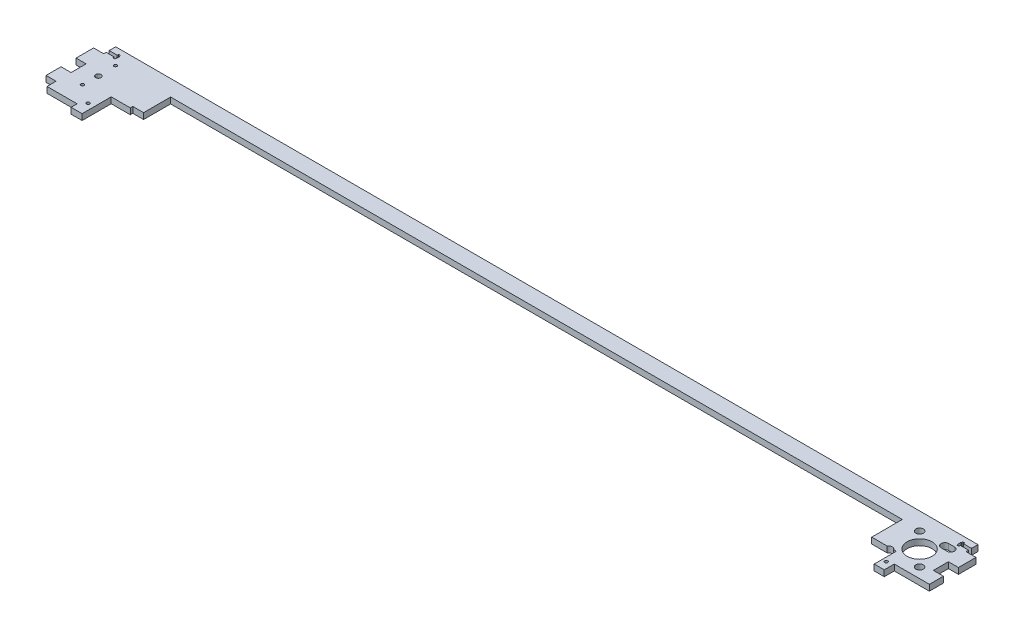
SolidWorks part; units mm, degrees
ref_plane "Płaszczyzna przednia" through (0, 0, 0) normal (0, 0, 1) x (1, 0, 0)
ref_plane "Płaszczyzna górna" through (0, 0, 0) normal (0, 1, 0) x (1, 0, 0)
ref_plane "Płaszczyzna prawa" through (0, 0, 0) normal (1, 0, 0) x (0, 0, -1)
sketch "Szkic1" plane through (0, -418.8763, -418.8763) normal (0, 1, 0) x (1, 0, 0)
  line L1 (-1145.3685, -408.8763) -> (-265.3685, -408.8763)
  line L2 (-1145.3685, -483.3763) -> (-1145.3685, -408.8763)
  line L3 (-265.3685, -408.8763) -> (-265.3685, -483.3763)
  line L4 (-1145.3685, -483.3763) -> (-265.3685, -483.3763)
  line L5 (-334.8685, -424.8763) -> (-1070.8685, -424.8763)
  line L6 (-334.8685, -424.8763) -> (-334.8685, -452.8763)
  line L7 (-334.8685, -452.8763) -> (-1070.8685, -452.8763)
  line L8 (-1070.8685, -424.8763) -> (-1070.8685, -452.8763)
  line L10 (-482.1641, -408.8763) -> (-356.3685, -408.8763) construction
  line L11 (-265.3685, -1108.8763) -> (-265.3685, -528.8763) construction
  dimension "D1" = 0
  dimension "D2" = 0
  dimension "D3" = 74.5
  dimension "D4" = 880
  dimension "D5" = 30.5
  dimension "D6" = 28
  dimension "D7" = 69.5
  dimension "D8" = 74.5
extrude "Dodanie-wyciągnięcie2" add sketch "Szkic1" along normal blind 3 and the other way blind 3
sketch "Szkic2" plane through (0, 0, 64.5) normal (0, 0, 1) x (1, 0, 0)
  line L0 (-1145.3685, -415.8763) -> (-265.3685, -415.8763) construction
  line L1 (-1145.3685, -421.8763) -> (-1105.3685, -421.8763)
  line L2 (-1145.3685, -421.8763) -> (-1145.3685, -415.8763)
  line L3 (-1145.3685, -415.8763) -> (-1105.3685, -415.8763)
  line L4 (-1105.3685, -421.8763) -> (-1105.3685, -415.8763)
  dimension "D1" = 40
extrude "Wytnij-wyciągnięcie1" cut sketch "Szkic2" against normal blind 6
pattern_linear "Szyk liniowy1" count 13 spacing 91 along (1, 0, 0) of "Wytnij-wyciągnięcie1"
sketch "Szkic3" plane through (0, -415.8763, 0) normal (0, 1, 0) x (1, 0, 0)
  line L0 (-1105.3685, -58.5) -> (-1145.3685, -58.5) construction
  line L1 (-1032.8185, -58.5) -> (-1035.9185, -58.5)
  line L2 (-1032.8185, -58.5) -> (-1032.8185, -54.5)
  line L3 (-1032.8185, -52) -> (-1035.9185, -52)
  line L4 (-1035.9185, -58.5) -> (-1035.9185, -54.5)
  line L5 (-1032.8185, -52.5) -> (-1032.8185, -52)
  line L6 (-1031.4435, -52.5) -> (-1032.8185, -52.5)
  line L7 (-1031.4435, -52.5) -> (-1031.4435, -54.5)
  line L8 (-1031.4435, -54.5) -> (-1032.8185, -54.5)
  line L9 (-1037.2935, -52.5) -> (-1037.2935, -54.5)
  line L10 (-1035.9185, -52.5) -> (-1037.2935, -52.5)
  line L11 (-1035.9185, -52.5) -> (-1035.9185, -52)
  line L12 (-1035.9185, -54.5) -> (-1037.2935, -54.5)
  line L14 (-1054.3685, -58.5) -> (-1054.3685, -64.5) construction
  point P14 (-1034.3685, -58.5)
  dimension "D1" = 6.5
  dimension "D2" = 3.1
  dimension "D3" = 5.85
  dimension "D4" = 1.375
  dimension "D5" = 0.5
  dimension "D6" = 2
  dimension "D7" = 20
extrude "Wytnij-wyciągnięcie2" cut sketch "Szkic3" against normal blind 6
sketch "Szkic4" plane through (0, -415.8763, 0) normal (0, 1, 0) x (1, 0, 0)
  line L0 (-1145.3685, 10) -> (-1145.3685, -58.5) construction
  line L1 (-1145.3685, -19.5) -> (-1135.3685, -19.5)
  line L2 (-1145.3685, -19.5) -> (-1145.3685, -34.5)
  line L3 (-1145.3685, -34.5) -> (-1135.3685, -34.5)
  line L4 (-1135.3685, -19.5) -> (-1135.3685, -34.5)
  line L6 (-1105.3685, -58.5) -> (-1145.3685, -58.5) construction
  line L8 (-1145.3685, -58.5) -> (-1135.3685, -58.5)
  line L9 (-1145.3685, -58.5) -> (-1145.3685, -49.5)
  line L10 (-1145.3685, -49.5) -> (-1135.3685, -49.5)
  line L11 (-1135.3685, -58.5) -> (-1135.3685, -49.5)
  line L12 (-1145.3685, 10) -> (-1135.3685, 10)
  line L13 (-1145.3685, 10) -> (-1145.3685, -2)
  line L14 (-1145.3685, -2) -> (-1135.3685, -2)
  line L15 (-1135.3685, 10) -> (-1135.3685, -2)
  dimension "D1" = 15
  dimension "D2" = 24
  dimension "D3" = 10
  dimension "D4" = 10
  dimension "D5" = 9
  dimension "D6" = 10
  dimension "D7" = 12
extrude "Wytnij-wyciągnięcie3" cut sketch "Szkic4" against normal blind 6
sketch "Szkic5" plane through (0, -415.8763, 0) normal (0, 1, 0) x (1, 0, 0)
  line L0 (-1135.3685, -34.5) -> (-1135.3685, -19.5) construction
  line L1 (-1135.3685, 3.55) -> (-1127.3685, 3.55)
  line L2 (-1135.3685, 3.55) -> (-1135.3685, 0.45)
  line L3 (-1135.3685, 0.45) -> (-1127.3685, 0.45)
  line L4 (-1124.8685, 3.55) -> (-1124.8685, 0.45)
  line L5 (-1125.3685, 3.55) -> (-1125.3685, 4.925)
  line L6 (-1125.3685, -0.925) -> (-1127.3685, -0.925)
  line L7 (-1125.3685, -0.925) -> (-1125.3685, 0.45)
  line L8 (-1125.3685, 4.925) -> (-1127.3685, 4.925)
  line L9 (-1127.3685, -0.925) -> (-1127.3685, 0.45)
  line L10 (-1125.3685, 0.45) -> (-1124.8685, 0.45)
  line L11 (-1127.3685, 3.55) -> (-1127.3685, 4.925)
  line L12 (-1125.3685, 3.55) -> (-1124.8685, 3.55)
  line L13 (-265.3685, 10) -> (-1135.3685, 10) construction
  point P14 (-1135.3685, 2)
  dimension "D1" = 3.1
  dimension "D2" = 0.5
  dimension "D3" = 5.85
  dimension "D4" = 1.375
  dimension "D5" = 2
  dimension "D6" = 10.5
  dimension "D7" = 8
extrude "Wytnij-wyciągnięcie4" cut sketch "Szkic5" against normal blind 6
ref_plane "Płaszczyzna1" through (-705.3685, 0, 0) normal (-1, 0, 0) x (0, 0, 1)
mirror "Lustro1" about plane through (-705.3685, 0, 0) normal (-1, 0, 0) of "Wytnij-wyciągnięcie4", "Wytnij-wyciągnięcie3"
sketch "Szkic6" plane through (0, -421.8763, 0) normal (0, -1, 0) x (1, 0, 0)
  circle A0 centre (-1118.7056, 24) radius 2.5 construction
  circle A8 centre (-1119.2648, 6.2898) radius 1.55 construction
  circle A9 centre (-1118.7056, 24) radius 8
  circle A10 centre (-1118.7056, 24) radius 2.7
  circle A11 centre (-1119.2648, 39.2898) radius 1.55 construction
  circle A12 centre (-1119.2648, 6.2898) radius 1.55
  circle A13 centre (-1119.2648, 39.2898) radius 1.55
  dimension "D1" = 0
sketch "Szkic8" plane through (0, -421.8763, 0) normal (0, -1, 0) x (1, 0, 0)
  circle A0 centre (-1119.2648, 39.2898) radius 1.55 construction
  circle A1 centre (-1119.2648, 39.2898) radius 1.55
  circle A4 centre (-1119.2648, 6.2898) radius 1.55 construction
  circle A7 centre (-1119.2648, 6.2898) radius 1.55
  circle A8 centre (-1118.7056, 24) radius 2.7 construction
  circle A10 centre (-1118.7056, 24) radius 2.7
extrude "Wytnij-wyciągnięcie5" cut sketch "Szkic8" against normal blind 6
sketch "Szkic9" plane through (0, -415.8763, 0) normal (0, 1, 0) x (1, 0, 0)
  circle A0 centre (-300.7063, -22.93) radius 2.5 construction
  circle A2 centre (-300.7063, -22.93) radius 12.5
  dimension "D1" = 25
  dimension "D2" = 0
extrude "Wytnij-wyciągnięcie6" cut sketch "Szkic9" against normal blind 6
sketch "Szkic10" plane through (0, -421.8763, 0) normal (0, -1, 0) x (1, 0, 0)
  circle A0 centre (-285.2063, 38.43) radius 1.55 construction
  circle A1 centre (-285.2063, 7.43) radius 1.55 construction
  circle A2 centre (-316.2063, 38.43) radius 1.55 construction
  circle A3 centre (-316.2063, 7.43) radius 1.55 construction
  circle A4 centre (-285.2063, 38.43) radius 1.55
  circle A5 centre (-285.2063, 7.43) radius 1.55
  circle A6 centre (-316.2063, 38.43) radius 1.55
  circle A7 centre (-316.2063, 7.43) radius 1.55
  circle A8 centre (-285.2063, 38.43) radius 3.75
  circle A9 centre (-285.2063, 7.43) radius 3.75
  circle A10 centre (-316.2063, 38.43) radius 3.75
  circle A11 centre (-316.2063, 7.43) radius 3.75
  dimension "D1" = 7.5
  dimension "D2" = 7.5
  dimension "D3" = 7.5
  dimension "D4" = 7.5
sketch "Szkic13" plane through (0, -415.8763, 0) normal (0, 1, 0) x (1, 0, 0)
  line L0 (-265.3685, -48.5) -> (-265.3685, -64.5)
  line L1 (-265.3685, -48.5) -> (-295.3685, -48.5)
  line L2 (-265.3685, -64.5) -> (-295.3685, -64.5)
  line L3 (-295.3685, -48.5) -> (-295.3685, -64.5)
  line L4 (-286.3685, -58.5) -> (-326.3685, -58.5) construction
  line L5 (-265.3685, -49.5) -> (-265.3685, -34.5) construction
  line L6 (-286.3685, -64.5) -> (-265.3685, -64.5) construction
  dimension "D1" = 0
  dimension "D2" = 30
  dimension "D3" = 0
  dimension "D4" = 10
extrude "Wytnij-wyciągnięcie8" cut sketch "Szkic13" against normal blind 6
pattern_linear "Szyk liniowy3" count 2 spacing 91 along (1, 0, 0) count 3 spacing 273 along (1, 0, 0) of "Wytnij-wyciągnięcie2"
sketch "Szkic14" plane through (0, -415.8763, 0) normal (0, 1, 0) x (1, 0, 0)
  line L111 (-319.9563, -36.5) -> (-1105.3685, -36.5)
  line L112 (-1105.3685, -36.5) -> (-1105.3685, -64.5)
  line L113 (-1105.3685, -64.5) -> (-1054.3685, -64.5)
  line L114 (-1054.3685, -64.5) -> (-1054.3685, -58.5)
  line L115 (-1054.3685, -58.5) -> (-1035.9185, -58.5)
  line L116 (-1035.9185, -58.5) -> (-1035.9185, -54.5)
  line L117 (-1035.9185, -54.5) -> (-1037.2935, -54.5)
  line L118 (-1037.2935, -54.5) -> (-1037.2935, -52.5)
  line L119 (-1037.2935, -52.5) -> (-1035.9185, -52.5)
  line L120 (-1035.9185, -52.5) -> (-1035.9185, -52)
  line L121 (-1035.9185, -52) -> (-1032.8185, -52)
  line L122 (-1032.8185, -52) -> (-1032.8185, -52.5)
  line L123 (-1032.8185, -52.5) -> (-1031.4435, -52.5)
  line L124 (-1031.4435, -52.5) -> (-1031.4435, -54.5)
  line L125 (-1031.4435, -54.5) -> (-1032.8185, -54.5)
  line L126 (-1032.8185, -54.5) -> (-1032.8185, -58.5)
  line L127 (-1032.8185, -58.5) -> (-1014.3685, -58.5)
  line L128 (-1014.3685, -58.5) -> (-1014.3685, -64.5)
  line L129 (-1014.3685, -64.5) -> (-963.3685, -64.5)
  line L130 (-963.3685, -64.5) -> (-963.3685, -58.5)
  line L131 (-963.3685, -58.5) -> (-944.9185, -58.5)
  line L132 (-319.9563, -36.5) -> (-1105.3685, -36.5)
  line L133 (-944.9185, -58.5) -> (-944.9185, -54.5)
  line L134 (-944.9185, -58.5) -> (-944.9185, -54.5)
  line L135 (-944.9185, -54.5) -> (-946.2935, -54.5)
  line L136 (-944.9185, -54.5) -> (-946.2935, -54.5)
  line L137 (-946.2935, -54.5) -> (-946.2935, -52.5)
  line L138 (-946.2935, -54.5) -> (-946.2935, -52.5)
  line L139 (-946.2935, -52.5) -> (-944.9185, -52.5)
  line L140 (-946.2935, -52.5) -> (-944.9185, -52.5)
  line L141 (-944.9185, -52.5) -> (-944.9185, -52)
  line L142 (-944.9185, -52.5) -> (-944.9185, -52)
  line L144 (-923.3685, -58.5) -> (-923.3685, -64.5)
  line L145 (-923.3685, -64.5) -> (-872.3685, -64.5)
  line L146 (-872.3685, -64.5) -> (-872.3685, -58.5)
  line L147 (-872.3685, -58.5) -> (-832.3685, -58.5)
  line L148 (-832.3685, -58.5) -> (-832.3685, -64.5)
  line L149 (-832.3685, -64.5) -> (-781.3685, -64.5)
  line L150 (-781.3685, -64.5) -> (-781.3685, -58.5)
  line L151 (-781.3685, -58.5) -> (-762.9185, -58.5)
  line L164 (-741.3685, -58.5) -> (-741.3685, -64.5)
  line L165 (-741.3685, -64.5) -> (-690.3685, -64.5)
  line L166 (-690.3685, -64.5) -> (-690.3685, -58.5)
  line L167 (-690.3685, -58.5) -> (-671.9185, -58.5)
  line L180 (-650.3685, -58.5) -> (-650.3685, -64.5)
  line L181 (-650.3685, -64.5) -> (-599.3685, -64.5)
  line L182 (-599.3685, -64.5) -> (-599.3685, -58.5)
  line L183 (-599.3685, -58.5) -> (-559.3685, -58.5)
  line L184 (-559.3685, -58.5) -> (-559.3685, -64.5)
  line L185 (-559.3685, -64.5) -> (-508.3685, -64.5)
  line L186 (-508.3685, -64.5) -> (-508.3685, -58.5)
  line L187 (-508.3685, -58.5) -> (-489.9185, -58.5)
  line L200 (-468.3685, -58.5) -> (-468.3685, -64.5)
  line L201 (-468.3685, -64.5) -> (-417.3685, -64.5)
  line L202 (-417.3685, -64.5) -> (-417.3685, -58.5)
  line L203 (-417.3685, -58.5) -> (-398.9185, -58.5)
  line L216 (-377.3685, -58.5) -> (-377.3685, -64.5)
  line L217 (-377.3685, -64.5) -> (-326.3685, -64.5)
  line L218 (-326.3685, -64.5) -> (-326.3685, -58.5)
  line L219 (-326.3685, -58.5) -> (-300.3685, -58.5)
  line L223 (-1105.3685, -36.5) -> (-1105.3685, -64.5)
  line L224 (-1105.3685, -64.5) -> (-1054.3685, -64.5)
  line L225 (-1054.3685, -64.5) -> (-1054.3685, -58.5)
  line L226 (-1054.3685, -58.5) -> (-1035.9185, -58.5)
  line L227 (-1035.9185, -58.5) -> (-1035.9185, -54.5)
  line L228 (-1035.9185, -54.5) -> (-1037.2935, -54.5)
  line L229 (-1037.2935, -54.5) -> (-1037.2935, -52.5)
  line L230 (-1037.2935, -52.5) -> (-1035.9185, -52.5)
  line L231 (-1035.9185, -52.5) -> (-1035.9185, -52)
  line L232 (-1035.9185, -52) -> (-1032.8185, -52)
  line L233 (-1032.8185, -52) -> (-1032.8185, -52.5)
  line L234 (-1032.8185, -52.5) -> (-1031.4435, -52.5)
  line L235 (-1031.4435, -52.5) -> (-1031.4435, -54.5)
  line L236 (-1031.4435, -54.5) -> (-1032.8185, -54.5)
  line L237 (-1032.8185, -54.5) -> (-1032.8185, -58.5)
  line L238 (-1032.8185, -58.5) -> (-1014.3685, -58.5)
  line L239 (-1014.3685, -58.5) -> (-1014.3685, -64.5)
  line L240 (-1014.3685, -64.5) -> (-963.3685, -64.5)
  line L241 (-963.3685, -64.5) -> (-963.3685, -58.5)
  line L242 (-963.3685, -58.5) -> (-944.9185, -58.5)
  line L255 (-923.3685, -58.5) -> (-923.3685, -64.5)
  line L256 (-923.3685, -64.5) -> (-872.3685, -64.5)
  line L257 (-872.3685, -64.5) -> (-872.3685, -58.5)
  line L258 (-872.3685, -58.5) -> (-832.3685, -58.5)
  line L259 (-832.3685, -58.5) -> (-832.3685, -64.5)
  line L260 (-832.3685, -64.5) -> (-781.3685, -64.5)
  line L261 (-781.3685, -64.5) -> (-781.3685, -58.5)
  line L262 (-781.3685, -58.5) -> (-762.9185, -58.5)
  line L275 (-741.3685, -58.5) -> (-741.3685, -64.5)
  line L276 (-741.3685, -64.5) -> (-690.3685, -64.5)
  line L277 (-690.3685, -64.5) -> (-690.3685, -58.5)
  line L278 (-690.3685, -58.5) -> (-671.9185, -58.5)
  line L291 (-650.3685, -58.5) -> (-650.3685, -64.5)
  line L292 (-650.3685, -64.5) -> (-599.3685, -64.5)
  line L293 (-599.3685, -64.5) -> (-599.3685, -58.5)
  line L294 (-599.3685, -58.5) -> (-559.3685, -58.5)
  line L295 (-559.3685, -58.5) -> (-559.3685, -64.5)
  line L296 (-559.3685, -64.5) -> (-508.3685, -64.5)
  line L297 (-508.3685, -64.5) -> (-508.3685, -58.5)
  line L298 (-508.3685, -58.5) -> (-489.9185, -58.5)
  line L311 (-468.3685, -58.5) -> (-468.3685, -64.5)
  line L312 (-468.3685, -64.5) -> (-417.3685, -64.5)
  line L313 (-417.3685, -64.5) -> (-417.3685, -58.5)
  line L314 (-417.3685, -58.5) -> (-398.9185, -58.5)
  line L327 (-377.3685, -58.5) -> (-377.3685, -64.5)
  line L328 (-377.3685, -64.5) -> (-326.3685, -64.5)
  line L329 (-326.3685, -64.5) -> (-326.3685, -58.5)
  line L330 (-326.3685, -58.5) -> (-300.3685, -58.5)
  line L503 (-944.9185, -52) -> (-941.8185, -52)
  line L504 (-944.9185, -52) -> (-941.8185, -52)
  line L507 (-941.8185, -52.5) -> (-940.4435, -52.5)
  line L508 (-941.8185, -52.5) -> (-940.4435, -52.5)
  line L509 (-940.4435, -52.5) -> (-940.4435, -54.5)
  line L510 (-940.4435, -52.5) -> (-940.4435, -54.5)
  line L511 (-940.4435, -54.5) -> (-941.8185, -54.5)
  line L512 (-940.4435, -54.5) -> (-941.8185, -54.5)
  line L513 (-941.8185, -54.5) -> (-941.8185, -58.5)
  line L514 (-941.8185, -54.5) -> (-941.8185, -58.5)
  line L515 (-941.8185, -58.5) -> (-923.3685, -58.5)
  line L516 (-941.8185, -58.5) -> (-923.3685, -58.5)
  line L517 (-762.9185, -58.5) -> (-762.9185, -54.5)
  line L518 (-762.9185, -58.5) -> (-762.9185, -54.5)
  line L519 (-762.9185, -54.5) -> (-764.2935, -54.5)
  line L520 (-762.9185, -54.5) -> (-764.2935, -54.5)
  line L521 (-764.2935, -54.5) -> (-764.2935, -52.5)
  line L522 (-764.2935, -54.5) -> (-764.2935, -52.5)
  line L523 (-764.2935, -52.5) -> (-762.9185, -52.5)
  line L524 (-764.2935, -52.5) -> (-762.9185, -52.5)
  line L525 (-762.9185, -52.5) -> (-762.9185, -52)
  line L526 (-762.9185, -52.5) -> (-762.9185, -52)
  line L527 (-762.9185, -52) -> (-759.8185, -52)
  line L528 (-762.9185, -52) -> (-759.8185, -52)
  line L529 (-759.8185, -52) -> (-759.8185, -52.5)
  line L530 (-759.8185, -52) -> (-759.8185, -52.5)
  line L531 (-759.8185, -52.5) -> (-758.4435, -52.5)
  line L532 (-759.8185, -52.5) -> (-758.4435, -52.5)
  line L533 (-758.4435, -52.5) -> (-758.4435, -54.5)
  line L534 (-758.4435, -52.5) -> (-758.4435, -54.5)
  line L535 (-758.4435, -54.5) -> (-759.8185, -54.5)
  line L536 (-758.4435, -54.5) -> (-759.8185, -54.5)
  line L537 (-759.8185, -54.5) -> (-759.8185, -58.5)
  line L538 (-759.8185, -54.5) -> (-759.8185, -58.5)
  line L539 (-759.8185, -58.5) -> (-741.3685, -58.5)
  line L540 (-759.8185, -58.5) -> (-741.3685, -58.5)
  line L541 (-671.9185, -58.5) -> (-671.9185, -54.5)
  line L542 (-671.9185, -58.5) -> (-671.9185, -54.5)
  line L543 (-671.9185, -54.5) -> (-673.2935, -54.5)
  line L544 (-671.9185, -54.5) -> (-673.2935, -54.5)
  line L545 (-673.2935, -54.5) -> (-673.2935, -52.5)
  line L546 (-673.2935, -54.5) -> (-673.2935, -52.5)
  line L547 (-673.2935, -52.5) -> (-671.9185, -52.5)
  line L548 (-673.2935, -52.5) -> (-671.9185, -52.5)
  line L549 (-671.9185, -52.5) -> (-671.9185, -52)
  line L550 (-671.9185, -52.5) -> (-671.9185, -52)
  line L551 (-671.9185, -52) -> (-668.8185, -52)
  line L552 (-671.9185, -52) -> (-668.8185, -52)
  line L553 (-668.8185, -52) -> (-668.8185, -52.5)
  line L554 (-668.8185, -52) -> (-668.8185, -52.5)
  line L555 (-668.8185, -52.5) -> (-667.4435, -52.5)
  line L556 (-668.8185, -52.5) -> (-667.4435, -52.5)
  line L557 (-667.4435, -52.5) -> (-667.4435, -54.5)
  line L558 (-667.4435, -52.5) -> (-667.4435, -54.5)
  line L559 (-667.4435, -54.5) -> (-668.8185, -54.5)
  line L560 (-667.4435, -54.5) -> (-668.8185, -54.5)
  line L561 (-668.8185, -54.5) -> (-668.8185, -58.5)
  line L562 (-668.8185, -54.5) -> (-668.8185, -58.5)
  line L563 (-668.8185, -58.5) -> (-650.3685, -58.5)
  line L564 (-668.8185, -58.5) -> (-650.3685, -58.5)
  line L565 (-489.9185, -58.5) -> (-489.9185, -54.5)
  line L566 (-489.9185, -58.5) -> (-489.9185, -54.5)
  line L567 (-489.9185, -54.5) -> (-491.2935, -54.5)
  line L568 (-489.9185, -54.5) -> (-491.2935, -54.5)
  line L569 (-491.2935, -54.5) -> (-491.2935, -52.5)
  line L570 (-491.2935, -54.5) -> (-491.2935, -52.5)
  line L571 (-491.2935, -52.5) -> (-489.9185, -52.5)
  line L572 (-491.2935, -52.5) -> (-489.9185, -52.5)
  line L573 (-489.9185, -52.5) -> (-489.9185, -52)
  line L574 (-489.9185, -52.5) -> (-489.9185, -52)
  line L575 (-489.9185, -52) -> (-486.8185, -52)
  line L576 (-489.9185, -52) -> (-486.8185, -52)
  line L577 (-486.8185, -52) -> (-486.8185, -52.5)
  line L578 (-486.8185, -52) -> (-486.8185, -52.5)
  line L579 (-486.8185, -52.5) -> (-485.4435, -52.5)
  line L580 (-486.8185, -52.5) -> (-485.4435, -52.5)
  line L581 (-485.4435, -52.5) -> (-485.4435, -54.5)
  line L582 (-485.4435, -52.5) -> (-485.4435, -54.5)
  line L583 (-485.4435, -54.5) -> (-486.8185, -54.5)
  line L584 (-485.4435, -54.5) -> (-486.8185, -54.5)
  line L585 (-486.8185, -54.5) -> (-486.8185, -58.5)
  line L586 (-486.8185, -54.5) -> (-486.8185, -58.5)
  line L587 (-486.8185, -58.5) -> (-468.3685, -58.5)
  line L588 (-486.8185, -58.5) -> (-468.3685, -58.5)
  line L589 (-398.9185, -58.5) -> (-398.9185, -54.5)
  line L590 (-398.9185, -58.5) -> (-398.9185, -54.5)
  line L591 (-398.9185, -54.5) -> (-400.2935, -54.5)
  line L592 (-398.9185, -54.5) -> (-400.2935, -54.5)
  line L593 (-400.2935, -54.5) -> (-400.2935, -52.5)
  line L594 (-400.2935, -54.5) -> (-400.2935, -52.5)
  line L595 (-400.2935, -52.5) -> (-398.9185, -52.5)
  line L596 (-400.2935, -52.5) -> (-398.9185, -52.5)
  line L597 (-398.9185, -52.5) -> (-398.9185, -52)
  line L598 (-398.9185, -52.5) -> (-398.9185, -52)
  line L599 (-398.9185, -52) -> (-395.8185, -52)
  line L600 (-398.9185, -52) -> (-395.8185, -52)
  line L601 (-395.8185, -52) -> (-395.8185, -52.5)
  line L602 (-395.8185, -52) -> (-395.8185, -52.5)
  line L603 (-395.8185, -52.5) -> (-394.4435, -52.5)
  line L604 (-395.8185, -52.5) -> (-394.4435, -52.5)
  line L605 (-394.4435, -52.5) -> (-394.4435, -54.5)
  line L606 (-394.4435, -52.5) -> (-394.4435, -54.5)
  line L607 (-394.4435, -54.5) -> (-395.8185, -54.5)
  line L608 (-394.4435, -54.5) -> (-395.8185, -54.5)
  line L609 (-395.8185, -54.5) -> (-395.8185, -58.5)
  line L610 (-395.8185, -54.5) -> (-395.8185, -58.5)
  line L611 (-395.8185, -58.5) -> (-377.3685, -58.5)
  line L612 (-395.8185, -58.5) -> (-377.3685, -58.5)
  line L621 (-319.9563, -38.43) -> (-319.9563, -36.5)
  line L622 (-319.9563, -38.43) -> (-319.9563, -36.5)
  line L1017 (-300.3685, -58.5) -> (-300.3685, -48.5)
  line L1018 (-300.3685, -58.5) -> (-300.3685, -48.5)
  line L1019 (-300.3685, -48.5) -> (-290.3685, -48.5)
  line L1020 (-300.3685, -48.5) -> (-290.3685, -48.5)
  line L2031 (-290.3685, -48.5) -> (-290.3685, -36.5)
  line L2032 (-290.3685, -48.5) -> (-290.3685, -36.5)
  line L2033 (-290.3685, -36.5) -> (-312.4563, -36.5)
  line L2034 (-290.3685, -36.5) -> (-312.4563, -36.5)
  line L2035 (-312.4563, -36.5) -> (-312.4563, -38.43)
  line L2036 (-312.4563, -36.5) -> (-312.4563, -38.43)
  line L3130 (-941.8185, -52) -> (-941.8185, -52.5)
  line L3131 (-941.8185, -52) -> (-941.8185, -52.5)
  arc A25 (-319.9563, -38.43) -> (-312.4563, -38.43) centre (-316.2063, -38.43) ccw
  arc A26 (-319.9563, -38.43) -> (-312.4563, -38.43) centre (-316.2063, -38.43) ccw
  dimension "D1" = 0
sketch "Szkic15" plane through (0, -415.8763, 0) normal (0, 1, 0) x (1, 0, 0)
  line L0 (-310.3662, -64.5) -> (-310.3662, -32.9692)
  line L1 (-310.3662, -64.5) -> (-1075.3684, -64.5)
  line L2 (-310.3662, -32.9692) -> (-1075.3684, -32.9692)
  line L3 (-1075.3684, -64.5) -> (-1075.3684, -32.9692)
  line L4 (-1105.3685, -36.5) -> (-1105.3685, -64.5) construction
  line L6 (-1105.3685, -64.5) -> (-1054.3685, -64.5) construction
  dimension "D1" = 30.0001
  dimension "D3" = 0
extrude "Wytnij-wyciągnięcie9" cut sketch "Szkic15" against normal blind 10
sketch "Szkic16" plane through (0, -415.8763, 0) normal (0, 1, 0) x (1, 0, 0)
  line L0 (-295.3685, -58.5) -> (-310.3662, -58.5) construction
  line L1 (-310.3662, -58.5) -> (-310.3662, -32.9692) construction
  line L3 (-1105.3685, -64.5) -> (-1075.3684, -64.5) construction
  line L4 (-1105.3685, -58.5) -> (-1105.3685, -64.5) construction
  circle A0 centre (-306.3662, -50.5) radius 1.55
  circle A2 centre (-1100.3685, -52.5) radius 1.55
  dimension "D1" = 8
  dimension "D3" = 4
  dimension "D5" = 3.1
  dimension "D9" = 3.1
  dimension "D10" = 12
  dimension "D11" = 5
extrude "Wytnij-wyciągnięcie10" cut sketch "Szkic16" against normal blind 10
sketch "Szkic17" plane through (0, -415.8763, 0) normal (0, 1, 0) x (1, 0, 0)
  line L0 (-1070.3685, -64.5) -> (-1094.3685, -64.5)
  line L1 (-1070.3685, -64.5) -> (-1070.3685, -35.4688)
  line L2 (-1094.3685, -64.5) -> (-1094.3685, -35.4688)
  line L3 (-1070.3685, -35.4688) -> (-1094.3685, -35.4688)
  line L4 (-1105.3685, -64.5) -> (-1075.3684, -64.5) construction
  line L6 (-1105.3685, -58.5) -> (-1105.3685, -64.5) construction
  line L7 (-1105.3685, -36.5) -> (-319.9563, -36.5) construction
  dimension "D1" = 11
  dimension "D2" = 1.0312
  dimension "D3" = 24
extrude "Wytnij-wyciągnięcie11" cut sketch "Szkic17" against normal blind 6
sketch "Szkic18" plane through (0, -421.8763, 0) normal (0, -1, 0) x (1, 0, 0)
  line L0 (-310.3662, 32.9692) -> (-334.8685, 32.9692)
  line L1 (-310.3662, 32.9692) -> (-310.3662, 36.5)
  line L2 (-334.8685, 32.9692) -> (-334.8685, 36.5)
  line L3 (-310.3662, 36.5) -> (-334.8685, 36.5)
  line L4 (-334.8685, 32.9692) -> (-310.3662, 32.9692) construction
  line L5 (-334.8685, 32.9692) -> (-334.8685, 6) construction
  line L6 (-1105.3685, 36.5) -> (-319.9563, 36.5) construction
  dimension "D1" = 0
  dimension "D2" = 0
sketch "Szkic20" plane through (0, -421.8763, 0) normal (0, -1, 0) x (1, 0, 0)
  line L0 (-295.3685, 48.5) -> (-290.3685, 48.5)
  line L1 (-295.3685, 48.5) -> (-295.3685, 58.5)
  line L2 (-290.3685, 48.5) -> (-290.3685, 58.5)
  line L3 (-295.3685, 58.5) -> (-290.3685, 58.5)
  line L4 (-265.3685, 48.5) -> (-295.3685, 48.5) construction
  line L5 (-310.3662, 58.5) -> (-295.3685, 58.5) construction
  line L6 (-290.3685, 36.5) -> (-290.3685, 48.5) construction
  dimension "D1" = 0
  dimension "D2" = 0
extrude "Dodanie-wyciągnięcie3" add sketch "Szkic20" against normal blind 6
extrude "Dodanie-wyciągnięcie4" add sketch "Szkic18" against normal blind 6
sketch "Szkic21" plane through (0, -415.8763, 0) normal (0, 1, 0) x (1, 0, 0)
  line L0 (-1070.8685, -6) -> (-1064.5685, -6)
  line L1 (-1070.8685, -6) -> (-1070.8685, -32.9692)
  line L2 (-1064.5685, -6) -> (-1064.5685, -32.9692)
  line L3 (-1070.8685, -32.9692) -> (-1064.5685, -32.9692)
  line L4 (-334.8685, -6) -> (-1070.8685, -6) construction
  line L5 (-1070.8685, -32.9692) -> (-1075.3684, -32.9692) construction
  dimension "D1" = 0
  dimension "D2" = 6.3
extrude "Dodanie-wyciągnięcie5" add sketch "Szkic21" against normal blind 6
sketch "Szkic22" plane through (0, -415.8763, 0) normal (0, 1, 0) x (1, 0, 0)
  line L0 (-290.3685, -58.5) -> (-300.3685, -58.5)
  line L1 (-290.3685, -58.5) -> (-290.3685, -48.5)
  line L2 (-300.3685, -58.5) -> (-300.3685, -48.5)
  line L3 (-290.3685, -48.5) -> (-300.3685, -48.5)
  line L4 (-290.3685, -58.5) -> (-310.3662, -58.5) construction
  line L5 (-300.3685, -48.5) -> (-290.3685, -48.5) construction
  line L6 (-300.3685, -58.5) -> (-300.3685, -48.5) construction
  dimension "D1" = 0
  dimension "D2" = 0
extrude "Wytnij-wyciągnięcie12" cut sketch "Szkic22" against normal blind 10
sketch "Szkic11" plane through (0, -421.8763, 0) normal (0, -1, 0) x (1, 0, 0)
  line L0 (-285.2063, 3.68) -> (-290.9343, 3.68)
  line L2 (-290.9343, 11.18) -> (-285.2063, 11.18)
  circle A0 centre (-285.2063, 38.43) radius 3.75 construction
  circle A1 centre (-285.2063, 7.43) radius 3.75 construction
  circle A2 centre (-285.2063, 38.43) radius 3.75
  arc A3 (-285.2063, 3.68) -> (-285.2063, 11.18) centre (-285.2063, 7.43) ccw
  circle A4 centre (-316.2063, 38.43) radius 3.75 construction
  circle A5 centre (-316.2063, 7.43) radius 3.75 construction
  circle A6 centre (-316.2063, 38.43) radius 3.75
  circle A7 centre (-316.2063, 7.43) radius 3.75
  arc A8 (-290.9343, 3.68) -> (-290.9343, 11.18) centre (-290.9343, 7.43) cw
extrude "Wytnij-wyciągnięcie7" cut sketch "Szkic11" against normal blind 6
equation "\"tolerancja_wpusy\"=0.2"
equation "\"dlugosc_wpustu_duzy\"=20"
equation "\"srednica_otworu_M3\"=3.1"
equation "\"szerokosc_nogi_T\"=3.1"
equation "\"dlugosc_T_30\"=11"
equation "\"grubosc_na_nakretke_kwadrat\"=2"
equation "\"szerokosc_na_nakretke_kwadrat\"=5.85"
equation "\"wyokosc_nadstawki_T\"=0.5"
equation "\"dlugosc_T_20_6\"=14"
equation "\"D2@Szkic3\"=\"szerokosc_nogi_T\""
equation "\"D3@Szkic3\"=\"szerokosc_na_nakretke_kwadrat\""
equation "\"D4@Szkic3\"=(\"szerokosc_na_nakretke_kwadrat\"-\"szerokosc_nogi_T\")/2"
equation "\"D5@Szkic3\"=\"wyokosc_nadstawki_T\""
equation "\"D6@Szkic3\"=\"grubosc_na_nakretke_kwadrat\""
equation "\"D1@Szkic5\"=\"szerokosc_nogi_T\""
equation "\"D2@Szkic5\"=\"wyokosc_nadstawki_T\""
equation "\"D3@Szkic5\"=\"szerokosc_na_nakretke_kwadrat\""
equation "\"D4@Szkic5\"=(\"szerokosc_na_nakretke_kwadrat\"-\"szerokosc_nogi_T\")/2"
equation "\"D5@Szkic5\"=\"grubosc_na_nakretke_kwadrat\""
equation "\"D5@Szkic16\"=\"srednica_otworu_M3\""
equation "\"D9@Szkic16\" = \"srednica_otworu_M3\""
